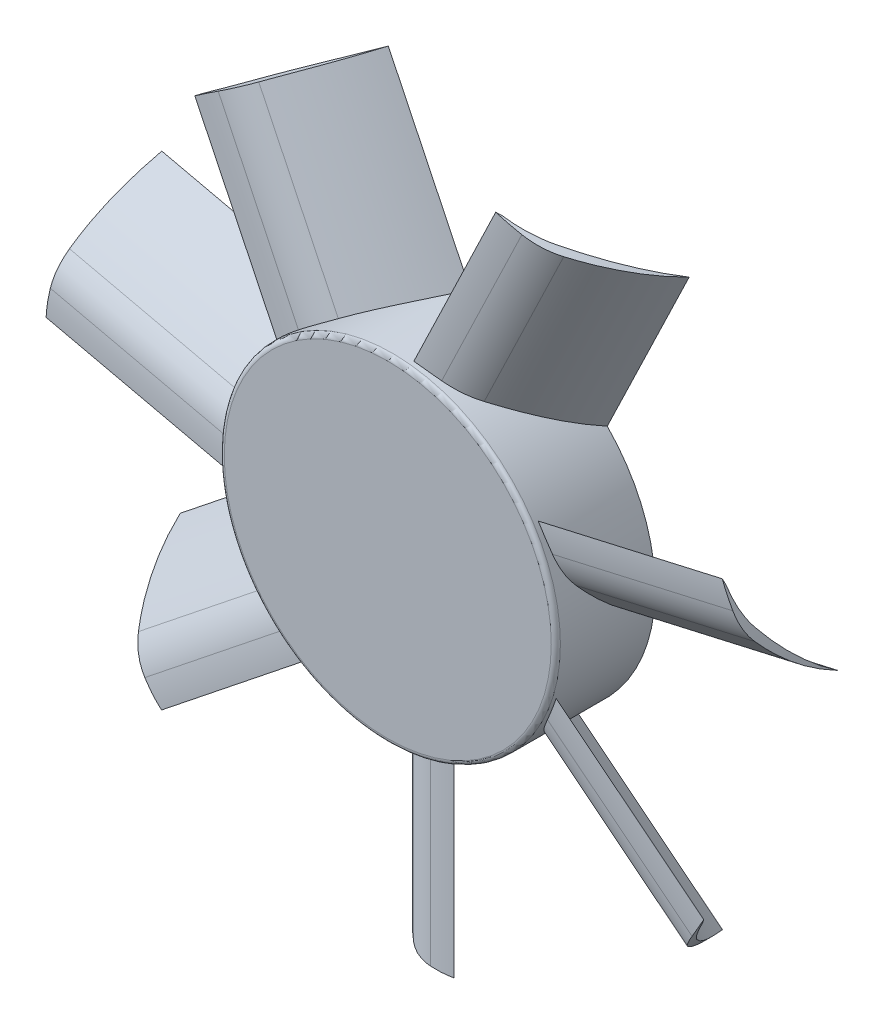
SolidWorks part; units mm, degrees
material "ПК/АБС"
ref_plane "Front" through (0, 0, 0) normal (0, 0, 1) x (1, 0, 0)
ref_plane "Top" through (0, 0, 0) normal (0, 1, 0) x (1, 0, 0)
ref_plane "Right" through (0, 0, 0) normal (1, 0, 0) x (0, 0, -1)
sketch "Эскиз1" plane through (0, 0, 0) normal (0, 0, 1) x (1, 0, 0)
  circle A0 centre (0, 0) radius 11
  dimension "D1" = 22
extrude "Бобышка-Вытянуть1" add sketch "Эскиз1" along normal blind 6.5
sketch "Эскиз2" plane through (0, 0, 0) normal (0, 0, -1) x (-1, 0, 0)
  circle A0 centre (0, 0) radius 9.75
  dimension "D1" = 19.5
extrude "Вырез-Вытянуть1" cut sketch "Эскиз2" against normal blind 5.5
sketch "Эскиз3" plane through (0, 0, 5.5) normal (0, 0, -1) x (-1, 0, 0)
  circle A0 centre (0, 0) radius 0.7
  dimension "D1" = 1.4
extrude "Бобышка-Вытянуть2" add sketch "Эскиз3" along normal blind 7.5
chamfer "Фаска1" distance 0.6 angle 45 1 edges at (-0.7, 0, -2)
sketch "Эскиз4" plane through (0, 0, 0) normal (0, 1, 0) x (1, 0, 0)
  line L0 (0, -6.5) -> (0, 0) construction
  line L1 (-11, -6.5) -> (11, -6.5) construction
  line L2 (0, 0) -> (11, -3.25) construction
  line L3 (11, -6.5) -> (11, 0) construction
  line L4 (11, -3.25) -> (-11, -3.25) construction
  line L5 (-11, 0) -> (-11, -6.5) construction
  line L7 (-3.75, -6.5) -> (3.75, -6.5) construction
  line L8 (-3.75, -6.5) -> (-3.75, 0) construction
  line L9 (-3.75, 0) -> (3.75, 0) construction
  line L10 (3.75, -6.5) -> (3.75, 0) construction
  line L11 (0, 0) -> (0, -6.5) construction
  line L12 (-3.75, -3.25) -> (3.75, -3.25) construction
  arc A2 (3.75, -5.9) -> (2.0764, -5.7876) centre (3.6109, 4.5482) cw
  arc A3 (0.0829, -4.887) -> (-3.75, 0) centre (9.9559, 6.8032) cw
  arc A4 (2.0764, -5.7876) -> (0.0829, -4.887) centre (2.6638, -1.831) cw
  arc A5 (3.75, -5.9) -> (3.4013, -5.7876) centre (6.34, 2.735) cw
  arc A6 (3.4013, -5.7876) -> (0.7393, -4.7108) centre (4.179, -0.0363) cw
  arc A7 (0.7393, -4.7108) -> (-3.75, 0) centre (11.8094, 10.3333) cw
  point P5 (0, -3.25)
  dimension "D3" = 0.6
  dimension "D4" = 4
  dimension "D1" = 6.5
  dimension "D2" = 7.5
extrude "Бобышка-Вытянуть3" add sketch "Эскиз4" against normal blind 23 from offset 10 offset against normal yes
pattern_circular "Круговой массив1" count 7 over 360 about axis through (0, 0, 6.5) along (0, 0, -1) of "Бобышка-Вытянуть3"
fillet "Скругление1" radius 0.3 1 edges at (11, 0, 6.5)
sketch "Эскиз5" plane through (0, 0, 6.5) normal (0, 0, 1) x (1, 0, 0)
  circle A0 centre (0, 0) radius 23
  dimension "D1" = 46
extrude "Вырез-Вытянуть2" cut sketch "Эскиз5" against normal blind 23 flip side to cut
